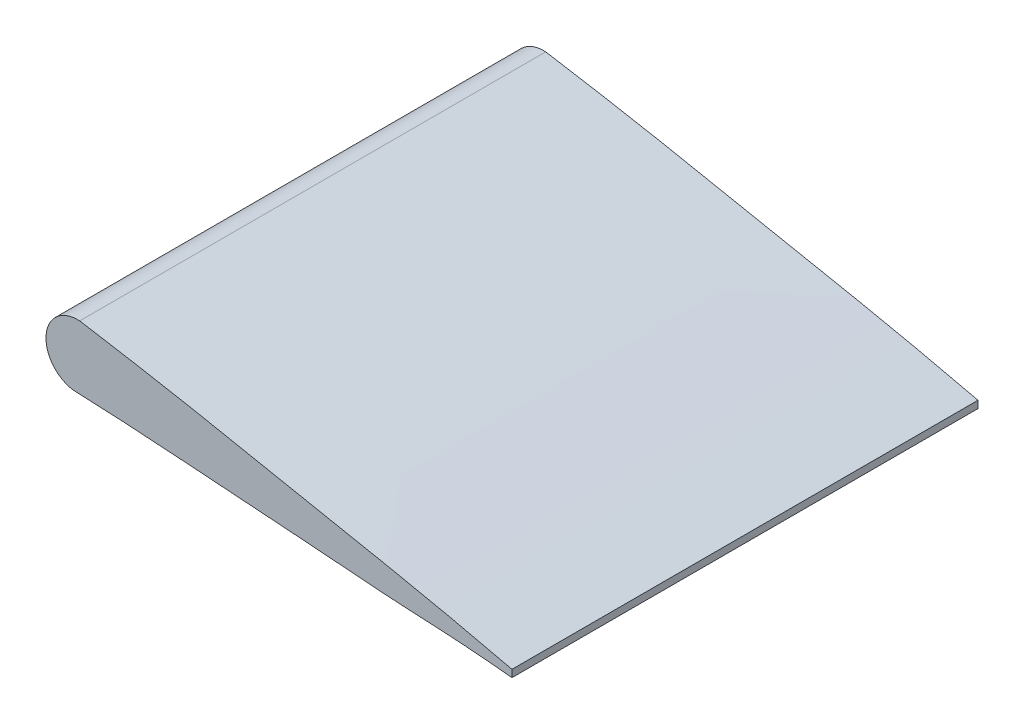
SolidWorks part; units mm, degrees
ref_plane "Front Plane" through (0, 0, 0) normal (0, 0, 1) x (1, 0, 0)
ref_plane "Top Plane" through (0, 0, 0) normal (0, 1, 0) x (1, 0, 0)
ref_plane "Right Plane" through (0, 0, 0) normal (1, 0, 0) x (0, 0, -1)
curve "Curve1"
  spline degree 3 poles (25.4, 0.0889, 0) (24.9755, 0.1879, 0) (24.1284, 0.3854, 0) (22.4316, 0.7474, 0) (20.3056, 1.1527, 0) (17.7661, 1.6728, 0) (15.2225, 2.1285, 0) (12.6828, 2.5208, 0) (10.1333, 2.7153, 0) (7.5886, 2.7177, 0) (5.4641, 2.6194, 0) (3.7724, 2.3478, 0) (2.7142, 2.0863, 0) (1.8702, 1.7836, 0) (1.2225, 1.4719, 0) (0.6864, 1.0854, 0) (0.2512, 0.6226, 0) (-0.1733, 0.0898, 0) (0.2557, -0.4257, 0) (0.7562, -0.3188, 0) (1.2698, -0.1979, 0) (1.905, -0.0426, 0) (2.7433, 0.1487, 0) (3.8055, 0.2872, 0) (5.4925, 0.5064, 0) (7.6119, 0.6227, 0) (10.1512, 0.7472, 0) (12.6929, 0.6952, 0) (15.2354, 0.6324, 0) (17.7755, 0.4534, 0) (20.3173, 0.2785, 0) (22.4335, 0.1017, 0) (24.1313, 0.0327, 0) (24.9769, -0.0484, 0) (25.4, -0.0889, 0) knots 0 0 0 0 0.025045 0.049982 0.099693 0.149405 0.198931 0.248178 0.297011 0.345669 0.394384 0.418982 0.444018 0.456913 0.470405 0.485361 0.494029 0.508284 0.517562 0.523649 0.536105 0.548579 0.561002 0.585562 0.610033 0.658766 0.707435 0.756094 0.804785 0.853571 0.902386 0.951201 0.975578 1 1 1 1
sketch "Sketch1" plane through (0, 0, 0) normal (0, 0, 1) x (1, 0, 0)
  line L0 (25.4, 0.0889) -> (25.4, -0.0889) construction
  line L1 (254, 0.889) -> (254, -0.889)
  line L2 (0, 0) -> (254, 0) construction
  line L3 (127, 0) -> (127, 24.8566) construction
  line L4 (139.7, 0) -> (139.7, 6.6099) construction
  line L5 (139.7, 6.6099) -> (139.7, 23.1662)
  line L6 (147.4934, 14.1005) -> (147.4934, 0) construction
  arc A0 (147.9779, 6.3222) -> (147.9779, 21.8788) centre (147.4934, 14.1005) cw
  spline S0 degree 3 poles (566.0092, 1924.6845) (86.0699, -40.1547) (57.6216, -6.7602) (22.4316, 0.7474) (20.3056, 1.1527) (17.7661, 1.6728) (15.2225, 2.1285) (12.6828, 2.5208) (10.1333, 2.7153) (7.5886, 2.7177) (5.4641, 2.6194) (3.7724, 2.3478) (2.7142, 2.0863) (1.8702, 1.7836) (1.2225, 1.4719) (0.6864, 1.0854) (0.2512, 0.6226) (-0.1733, 0.0898) (0.2557, -0.4257) (0.7562, -0.3188) (1.2698, -0.1979) (1.905, -0.0426) (2.7433, 0.1487) (3.8055, 0.2872) (5.4925, 0.5064) (7.6119, 0.6227) (10.1512, 0.7472) (12.6929, 0.6952) (15.2354, 0.6324) (17.7755, 0.4534) (20.3173, 0.2785) (22.4335, 0.1017) (47.7216, -0.9264) (69.4681, -40.4772) (235.2289, 1988.3291) knots -1.967795 -1.967795 -1.967795 -1.967795 0.025045 0.049982 0.099693 0.149405 0.198931 0.248178 0.297011 0.345669 0.394384 0.418982 0.444018 0.456913 0.470405 0.485361 0.494029 0.508284 0.517562 0.523649 0.536105 0.548579 0.561002 0.585562 0.610033 0.658766 0.707435 0.756094 0.804785 0.853571 0.902386 0.951201 0.975578 2.356301 2.356301 2.356301 2.356301 only from (25.4, 0.0889) to (25.4, -0.0889) construction
  spline S1 degree 3 poles (25.4, 0.0889) (24.9755, 0.1879) (24.1284, 0.3854) (22.4316, 0.7474) (20.3056, 1.1527) (17.7661, 1.6728) (15.2225, 2.1285) (12.6828, 2.5208) (10.1333, 2.7153) (7.5886, 2.7177) (5.4641, 2.6194) (3.7724, 2.3478) (2.7142, 2.0863) (1.8702, 1.7836) (1.2225, 1.4719) (0.6864, 1.0854) (0.2512, 0.6226) (-0.1733, 0.0898) (0.2557, -0.4257) (0.7562, -0.3188) (1.2698, -0.1979) (1.905, -0.0426) (2.7433, 0.1487) (3.8055, 0.2872) (5.4925, 0.5064) (7.6119, 0.6227) (10.1512, 0.7472) (12.6929, 0.6952) (15.2354, 0.6324) (17.7755, 0.4534) (20.3173, 0.2785) (22.4335, 0.1017) (24.1313, 0.0327) (24.9769, -0.0484) (25.4, -0.0889) knots 0 0 0 0 0.025045 0.049982 0.099693 0.149405 0.198931 0.248178 0.297011 0.345669 0.394384 0.418982 0.444018 0.456913 0.470405 0.485361 0.494029 0.508284 0.517562 0.523649 0.536105 0.548579 0.561002 0.585562 0.610033 0.658766 0.707435 0.756094 0.804785 0.853571 0.902386 0.951201 0.975578 1 1 1 1 construction
  spline S2 degree 3 poles (254, 0.889) (249.7553, 1.8786) (241.2842, 3.8535) (224.3158, 7.4736) (203.0565, 11.5272) (177.6613, 16.7283) (152.2253, 21.2846) (126.8284, 25.208) (101.3332, 27.1529) (75.8856, 27.1773) (54.6411, 26.1945) (37.7241, 23.4783) (27.1418, 20.8628) (18.7017, 17.8364) (12.2246, 14.7192) (6.8643, 10.8535) (2.5124, 6.2258) (-1.7329, 0.8975) (2.5571, -4.257) (7.5624, -3.188) (12.6982, -1.9788) (19.0498, -0.4259) (27.4332, 1.4865) (38.0551, 2.8725) (54.9249, 5.0635) (76.1187, 6.227) (101.5119, 7.4722) (126.9288, 6.9519) (152.354, 6.3244) (177.755, 4.534) (203.1733, 2.7851) (224.3353, 1.0168) (241.3134, 0.3266) (249.7685, -0.4836) (254, -0.889) knots 0 0 0 0 0.025045 0.049982 0.099693 0.149405 0.198931 0.248178 0.297011 0.345669 0.394384 0.418982 0.444018 0.456913 0.470405 0.485361 0.494029 0.508284 0.517562 0.523649 0.536105 0.548579 0.561002 0.585562 0.610033 0.658766 0.707435 0.756094 0.804785 0.853571 0.902386 0.951201 0.975578 1 1 1 1
  point P9 (139.7, 0)
  point P12 (139.7, 14.888)
  point P14 (147.9779, 6.3222)
  dimension "D1" = 254
  dimension "D2" = 24.8566
  dimension "D3" = 139.7
  dimension "D4" = 8.2779
extrude "Boss-Extrude1" add sketch "Sketch1" along normal blind 114.3 contours L1 S2 A0 region at (183.3979, 9.6461, 0)
